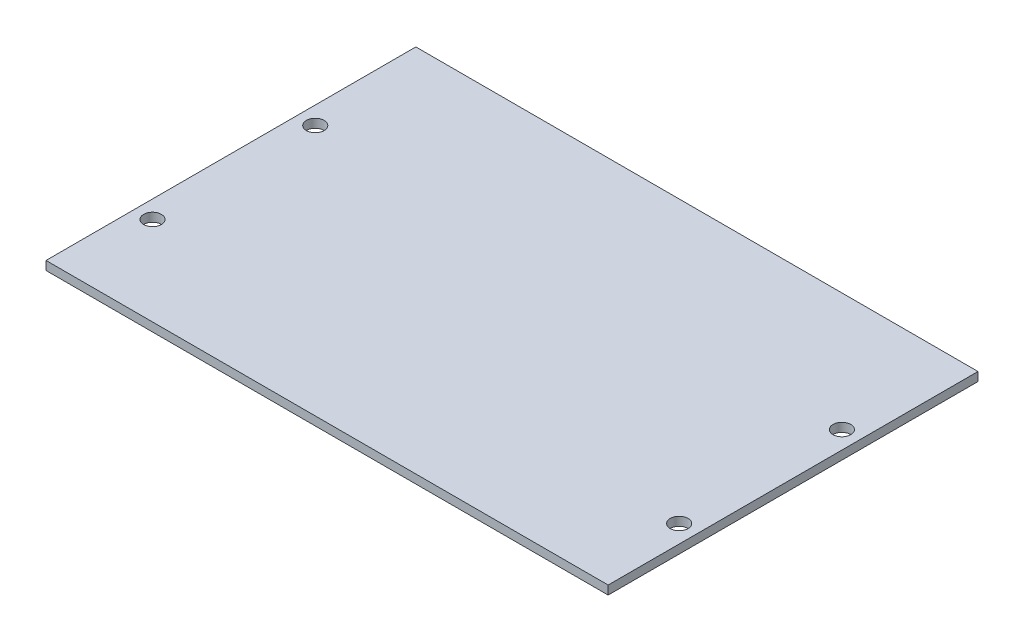
SolidWorks part; units mm, degrees
ref_plane "Front Plane" through (0, 0, 0) normal (0, 0, 1) x (1, 0, 0)
ref_plane "Top Plane" through (0, 0, 0) normal (0, 1, 0) x (1, 0, 0)
ref_plane "Right Plane" through (0, 0, 0) normal (1, 0, 0) x (0, 0, -1)
sketch "Sketch1" plane through (0, 0, 0) normal (0, 1, 0) x (1, 0, 0)
  line L1 (-66.0198, 35.0258) -> (30.5002, 35.0258)
  line L2 (-66.0198, 35.0258) -> (-66.0198, -28.4742)
  line L3 (-66.0198, -28.4742) -> (30.5002, -28.4742)
  line L4 (30.5002, 35.0258) -> (30.5002, -28.4742)
  dimension "D1" = 63.5
  dimension "D2" = 96.52
extrude "Boss-Extrude1" add sketch "Sketch1" along normal blind 1.4986
sketch "Sketch2" plane through (0, 1.4986, 0) normal (0, 1, 0) x (1, 0, 0)
  line L0 (-66.0198, 35.0258) -> (-66.0198, -28.4742) construction
  line L2 (-66.0198, -28.4742) -> (30.5002, -28.4742) construction
  circle A0 centre (-62.9718, 14.7058) radius 1.524
  circle A1 centre (-62.9718, -13.2342) radius 1.524
  circle A2 centre (27.4522, 14.7058) radius 1.524
  circle A3 centre (27.4522, -13.2342) radius 1.524
  dimension "D3" = 93.472
  dimension "D1" = 3.048
  dimension "D2" = 43.18
  dimension "D4" = 15.24
extrude "mouting holes" cut sketch "Sketch2" against normal up to surface (1.4986 mm away) up to face at (-17.7598, 0, -3.2758)
